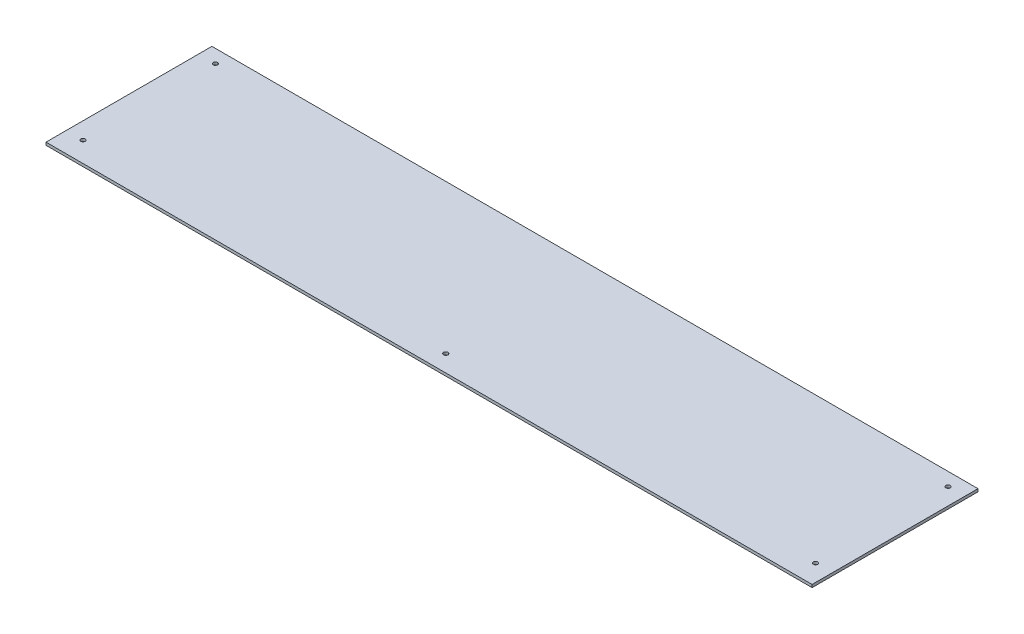
SolidWorks part; units mm, degrees
ref_plane "Alzado" through (0, 0, 0) normal (0, 0, 1) x (1, 0, 0)
ref_plane "Planta" through (0, 0, 0) normal (0, 1, 0) x (1, 0, 0)
ref_plane "Vista lateral" through (0, 0, 0) normal (1, 0, 0) x (0, 0, -1)
sketch "Croquis1" plane through (0, 0, 0) normal (0, 1, 0) x (1, 0, 0)
  line L0 (275.25, 120) -> (275.25, 0) construction
  line L1 (0, 0) -> (550.5, 0)
  line L2 (0, 0) -> (0, 120)
  line L3 (0, 120) -> (550.5, 120)
  line L4 (550.5, 0) -> (550.5, 120)
  line L5 (0, 60) -> (550.5, 60) construction
  circle A0 centre (12.5, 15) radius 1.55
  circle A1 centre (12.5, 110) radius 1.55
  circle A2 centre (538, 15) radius 1.55
  circle A3 centre (538, 110) radius 1.55
  dimension "D3" = 3.1
  dimension "D1" = 120
  dimension "D2" = 550.5
  dimension "D4" = 15
  dimension "D5" = 12.5
  dimension "D6" = 12.5
  dimension "D7" = 10
extrude "Saliente-Extruir1" add sketch "Croquis1" along normal blind 2
sketch "Croquis2" plane through (0, 0, 0) normal (0, -1, 0) x (1, 0, 0)
  line L0 (550, -0.5) -> (0.5, -0.5)
  line L1 (0.5, -0.5) -> (0.5, -119.5)
  line L2 (0.5, -119.5) -> (550, -119.5)
  line L3 (550, -119.5) -> (550, -0.5)
  line L4 (0, 0) -> (0, -120)
  line L5 (0, -120) -> (550.5, -120)
  line L6 (550.5, -120) -> (550.5, 0)
  line L7 (550.5, 0) -> (0, 0)
  line L8 (0, 0) -> (0, -120)
  line L9 (0, -120) -> (550.5, -120)
  line L10 (550.5, -120) -> (550.5, 0)
  line L11 (550.5, 0) -> (0, 0)
  dimension "D1" = 0
  dimension "D2" = 0.5
extrude "Cortar-Extruir1" cut sketch "Croquis2" against normal up to surface (2 mm away) up to face at (275.25, 2, -60)
sketch "Croquis3" plane through (0, 0, 0) normal (0, -1, 0) x (1, 0, 0)
  line L0 (275.25, -0.5) -> (275.25, -119.5) construction
  line L1 (550, -0.5) -> (0.5, -0.5) construction
  line L2 (0.5, -119.5) -> (550, -119.5) construction
  circle A0 centre (275.25, -12.5) radius 1.6
  dimension "D1" = 3.2
  dimension "D2" = 12
extrude "Cortar-Extruir2" cut sketch "Croquis3" against normal up to surface (2 mm away) up to face at (538, 2, -111.55)
